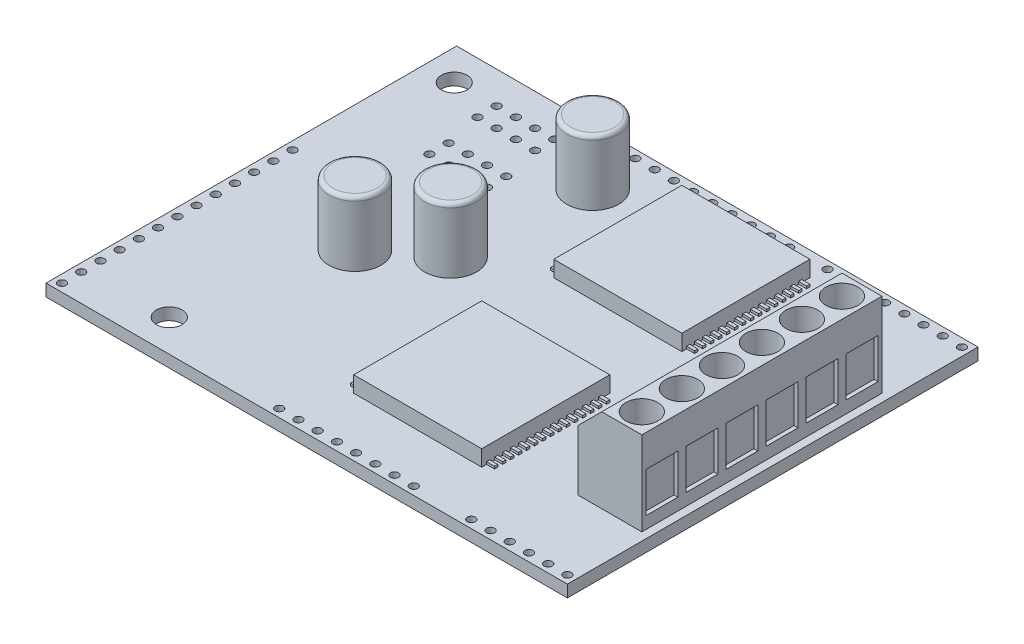
SolidWorks part; units mm, degrees
ref_plane "Спереди" through (0, 0, 0) normal (0, 0, 1) x (1, 0, 0)
ref_plane "Сверху" through (0, 0, 0) normal (0, 1, 0) x (1, 0, 0)
ref_plane "Справа" through (0, 0, 0) normal (1, 0, 0) x (0, 0, -1)
sketch "Эскиз1" plane through (0, 0, 0) normal (0, 1, 0) x (1, 0, 0)
  line L1 (-32.57, 25.65) -> (32.57, 25.65)
  line L2 (-32.57, 25.65) -> (-32.57, -25.65)
  line L3 (-32.57, -25.65) -> (32.57, -25.65)
  line L4 (32.57, 25.65) -> (32.57, -25.65)
  dimension "D1" = 65.14
  dimension "D2" = 51.3
  dimension "D3" = 32.57
  dimension "D4" = 25.65
extrude "Бобышка-Вытянуть1" add sketch "Эскиз1" along normal blind 1.5
sketch "Эскиз2" plane through (0, 1.5, 0) normal (0, 1, 0) x (1, 0, 0)
  line L0 (32.57, -25.65) -> (32.57, 25.65) construction
  line L1 (-1.43, 22.65) -> (14.57, 22.65)
  line L2 (-1.43, 22.65) -> (-1.43, 6.65)
  line L3 (-1.43, 6.65) -> (14.57, 6.65)
  line L4 (14.57, 22.65) -> (14.57, 6.65)
  line L5 (32.57, 25.65) -> (-32.57, 25.65) construction
  line L6 (-1.43, -2.35) -> (14.57, -2.35)
  line L7 (-1.43, -2.35) -> (-1.43, -18.35)
  line L8 (-1.43, -18.35) -> (14.57, -18.35)
  line L9 (14.57, -2.35) -> (14.57, -18.35)
  dimension "D1" = 16
  dimension "D2" = 16
  dimension "D3" = 18
  dimension "D4" = 3
  dimension "D5" = 2
extrude "Бобышка-Вытянуть2" add sketch "Эскиз2" along normal blind 2
sketch "Эскиз3" plane through (0, 1.5, 0) normal (0, 1, 0) x (1, 0, 0)
  line L0 (14.57, 6.65) -> (14.57, 22.65) construction
  line L1 (14.57, 21.65) -> (15.57, 21.65)
  line L2 (14.57, 21.65) -> (14.57, 21.25)
  line L3 (14.57, 21.25) -> (15.57, 21.25)
  line L4 (15.57, 21.65) -> (15.57, 21.25)
  line L5 (14.57, 22.65) -> (-1.43, 22.65) construction
  line L6 (14.57, 20.65) -> (15.57, 20.65)
  line L7 (14.57, 20.65) -> (14.57, 20.25)
  line L8 (14.57, 20.25) -> (15.57, 20.25)
  line L9 (15.57, 20.65) -> (15.57, 20.25)
  line L10 (14.57, 19.65) -> (15.57, 19.65)
  line L11 (14.57, 19.65) -> (14.57, 19.25)
  line L12 (14.57, 19.25) -> (15.57, 19.25)
  line L13 (15.57, 19.65) -> (15.57, 19.25)
  line L14 (14.57, 18.65) -> (15.57, 18.65)
  line L15 (14.57, 18.65) -> (14.57, 18.25)
  line L16 (14.57, 18.25) -> (15.57, 18.25)
  line L17 (15.57, 18.65) -> (15.57, 18.25)
  line L18 (14.57, 17.65) -> (15.57, 17.65)
  line L19 (14.57, 17.65) -> (14.57, 17.25)
  line L20 (14.57, 17.25) -> (15.57, 17.25)
  line L21 (15.57, 17.65) -> (15.57, 17.25)
  line L22 (14.57, 16.65) -> (15.57, 16.65)
  line L23 (14.57, 16.65) -> (14.57, 16.25)
  line L24 (14.57, 16.25) -> (15.57, 16.25)
  line L25 (15.57, 16.65) -> (15.57, 16.25)
  line L26 (14.57, 15.65) -> (15.57, 15.65)
  line L27 (14.57, 15.65) -> (14.57, 15.25)
  line L28 (14.57, 15.25) -> (15.57, 15.25)
  line L29 (15.57, 15.65) -> (15.57, 15.25)
  line L30 (14.57, 14.65) -> (15.57, 14.65)
  line L31 (14.57, 14.65) -> (14.57, 14.25)
  line L32 (14.57, 14.25) -> (15.57, 14.25)
  line L33 (15.57, 14.65) -> (15.57, 14.25)
  line L34 (14.57, 13.65) -> (15.57, 13.65)
  line L35 (14.57, 13.65) -> (14.57, 13.25)
  line L36 (14.57, 13.25) -> (15.57, 13.25)
  line L37 (15.57, 13.65) -> (15.57, 13.25)
  line L38 (14.57, 12.65) -> (15.57, 12.65)
  line L39 (14.57, 12.65) -> (14.57, 12.25)
  line L40 (14.57, 12.25) -> (15.57, 12.25)
  line L41 (15.57, 12.65) -> (15.57, 12.25)
  line L42 (14.57, 11.65) -> (15.57, 11.65)
  line L43 (14.57, 11.65) -> (14.57, 11.25)
  line L44 (14.57, 11.25) -> (15.57, 11.25)
  line L45 (15.57, 11.65) -> (15.57, 11.25)
  line L46 (14.57, 10.65) -> (15.57, 10.65)
  line L47 (14.57, 10.65) -> (14.57, 10.25)
  line L48 (14.57, 10.25) -> (15.57, 10.25)
  line L49 (15.57, 10.65) -> (15.57, 10.25)
  line L50 (14.57, 9.65) -> (15.57, 9.65)
  line L51 (14.57, 9.65) -> (14.57, 9.25)
  line L52 (14.57, 9.25) -> (15.57, 9.25)
  line L53 (15.57, 9.65) -> (15.57, 9.25)
  line L54 (14.57, 8.65) -> (15.57, 8.65)
  line L55 (14.57, 8.65) -> (14.57, 8.25)
  line L56 (14.57, 8.25) -> (15.57, 8.25)
  line L57 (15.57, 8.65) -> (15.57, 8.25)
  line L58 (14.57, 7.65) -> (15.57, 7.65)
  line L59 (14.57, 7.65) -> (14.57, 7.25)
  line L60 (14.57, 7.25) -> (15.57, 7.25)
  line L61 (15.57, 7.65) -> (15.57, 7.25)
  line L62 (6.57, 54.7714) -> (6.57, -83.906) construction
  line L63 (-2.43, 7.65) -> (-2.43, 7.25)
  line L64 (-1.43, 7.25) -> (-2.43, 7.25)
  line L65 (-1.43, 7.65) -> (-1.43, 7.25)
  line L66 (-1.43, 7.65) -> (-2.43, 7.65)
  line L67 (-2.43, 8.65) -> (-2.43, 8.25)
  line L68 (-1.43, 8.25) -> (-2.43, 8.25)
  line L69 (-1.43, 8.65) -> (-1.43, 8.25)
  line L70 (-1.43, 8.65) -> (-2.43, 8.65)
  line L71 (-2.43, 9.65) -> (-2.43, 9.25)
  line L72 (-1.43, 9.25) -> (-2.43, 9.25)
  line L73 (-1.43, 9.65) -> (-1.43, 9.25)
  line L74 (-1.43, 9.65) -> (-2.43, 9.65)
  line L75 (-2.43, 10.65) -> (-2.43, 10.25)
  line L76 (-1.43, 10.25) -> (-2.43, 10.25)
  line L77 (-1.43, 10.65) -> (-1.43, 10.25)
  line L78 (-1.43, 10.65) -> (-2.43, 10.65)
  line L79 (-2.43, 11.65) -> (-2.43, 11.25)
  line L80 (-1.43, 11.25) -> (-2.43, 11.25)
  line L81 (-1.43, 11.65) -> (-1.43, 11.25)
  line L82 (-1.43, 11.65) -> (-2.43, 11.65)
  line L83 (-2.43, 12.65) -> (-2.43, 12.25)
  line L84 (-1.43, 12.25) -> (-2.43, 12.25)
  line L85 (-1.43, 12.65) -> (-1.43, 12.25)
  line L86 (-1.43, 12.65) -> (-2.43, 12.65)
  line L87 (-2.43, 13.65) -> (-2.43, 13.25)
  line L88 (-1.43, 13.25) -> (-2.43, 13.25)
  line L89 (-1.43, 13.65) -> (-1.43, 13.25)
  line L90 (-1.43, 13.65) -> (-2.43, 13.65)
  line L91 (-2.43, 14.65) -> (-2.43, 14.25)
  line L92 (-1.43, 14.25) -> (-2.43, 14.25)
  line L93 (-1.43, 14.65) -> (-1.43, 14.25)
  line L94 (-1.43, 14.65) -> (-2.43, 14.65)
  line L95 (-2.43, 15.65) -> (-2.43, 15.25)
  line L96 (-1.43, 15.25) -> (-2.43, 15.25)
  line L97 (-1.43, 15.65) -> (-1.43, 15.25)
  line L98 (-1.43, 15.65) -> (-2.43, 15.65)
  line L99 (-2.43, 16.65) -> (-2.43, 16.25)
  line L100 (-1.43, 16.25) -> (-2.43, 16.25)
  line L101 (-1.43, 16.65) -> (-1.43, 16.25)
  line L102 (-1.43, 16.65) -> (-2.43, 16.65)
  line L103 (-2.43, 17.65) -> (-2.43, 17.25)
  line L104 (-1.43, 17.25) -> (-2.43, 17.25)
  line L105 (-1.43, 17.65) -> (-1.43, 17.25)
  line L106 (-1.43, 17.65) -> (-2.43, 17.65)
  line L107 (-2.43, 18.65) -> (-2.43, 18.25)
  line L108 (-1.43, 18.25) -> (-2.43, 18.25)
  line L109 (-1.43, 18.65) -> (-1.43, 18.25)
  line L110 (-1.43, 18.65) -> (-2.43, 18.65)
  line L111 (-2.43, 19.65) -> (-2.43, 19.25)
  line L112 (-1.43, 19.25) -> (-2.43, 19.25)
  line L113 (-1.43, 19.65) -> (-1.43, 19.25)
  line L114 (-1.43, 19.65) -> (-2.43, 19.65)
  line L115 (-2.43, 20.65) -> (-2.43, 20.25)
  line L116 (-1.43, 20.25) -> (-2.43, 20.25)
  line L117 (-1.43, 20.65) -> (-1.43, 20.25)
  line L118 (-1.43, 20.65) -> (-2.43, 20.65)
  line L119 (-2.43, 21.65) -> (-2.43, 21.25)
  line L120 (-1.43, 21.25) -> (-2.43, 21.25)
  line L121 (-1.43, 21.65) -> (-1.43, 21.25)
  line L122 (-1.43, 21.65) -> (-2.43, 21.65)
  line L123 (14.57, -3.35) -> (15.57, -3.35)
  line L124 (14.57, -3.35) -> (14.57, -3.75)
  line L125 (14.57, -3.75) -> (15.57, -3.75)
  line L126 (15.57, -3.35) -> (15.57, -3.75)
  line L127 (14.57, -4.35) -> (15.57, -4.35)
  line L128 (14.57, -4.35) -> (14.57, -4.75)
  line L129 (14.57, -4.75) -> (15.57, -4.75)
  line L130 (15.57, -4.35) -> (15.57, -4.75)
  line L131 (14.57, -5.35) -> (15.57, -5.35)
  line L132 (14.57, -5.35) -> (14.57, -5.75)
  line L133 (14.57, -5.75) -> (15.57, -5.75)
  line L134 (15.57, -5.35) -> (15.57, -5.75)
  line L135 (14.57, -6.35) -> (15.57, -6.35)
  line L136 (14.57, -6.35) -> (14.57, -6.75)
  line L137 (14.57, -6.75) -> (15.57, -6.75)
  line L138 (15.57, -6.35) -> (15.57, -6.75)
  line L139 (14.57, -7.35) -> (15.57, -7.35)
  line L140 (14.57, -7.35) -> (14.57, -7.75)
  line L141 (14.57, -7.75) -> (15.57, -7.75)
  line L142 (15.57, -7.35) -> (15.57, -7.75)
  line L143 (14.57, -8.35) -> (15.57, -8.35)
  line L144 (14.57, -8.35) -> (14.57, -8.75)
  line L145 (14.57, -8.75) -> (15.57, -8.75)
  line L146 (15.57, -8.35) -> (15.57, -8.75)
  line L147 (14.57, -9.35) -> (15.57, -9.35)
  line L148 (14.57, -9.35) -> (14.57, -9.75)
  line L149 (14.57, -9.75) -> (15.57, -9.75)
  line L150 (15.57, -9.35) -> (15.57, -9.75)
  line L151 (14.57, -10.35) -> (15.57, -10.35)
  line L152 (14.57, -10.35) -> (14.57, -10.75)
  line L153 (14.57, -10.75) -> (15.57, -10.75)
  line L154 (15.57, -10.35) -> (15.57, -10.75)
  line L155 (14.57, -11.35) -> (15.57, -11.35)
  line L156 (14.57, -11.35) -> (14.57, -11.75)
  line L157 (14.57, -11.75) -> (15.57, -11.75)
  line L158 (15.57, -11.35) -> (15.57, -11.75)
  line L159 (14.57, -12.35) -> (15.57, -12.35)
  line L160 (14.57, -12.35) -> (14.57, -12.75)
  line L161 (14.57, -12.75) -> (15.57, -12.75)
  line L162 (15.57, -12.35) -> (15.57, -12.75)
  line L163 (14.57, -13.35) -> (15.57, -13.35)
  line L164 (14.57, -13.35) -> (14.57, -13.75)
  line L165 (14.57, -13.75) -> (15.57, -13.75)
  line L166 (15.57, -13.35) -> (15.57, -13.75)
  line L167 (14.57, -14.35) -> (15.57, -14.35)
  line L168 (14.57, -14.35) -> (14.57, -14.75)
  line L169 (14.57, -14.75) -> (15.57, -14.75)
  line L170 (15.57, -14.35) -> (15.57, -14.75)
  line L171 (14.57, -15.35) -> (15.57, -15.35)
  line L172 (14.57, -15.35) -> (14.57, -15.75)
  line L173 (14.57, -15.75) -> (15.57, -15.75)
  line L174 (15.57, -15.35) -> (15.57, -15.75)
  line L175 (14.57, -16.35) -> (15.57, -16.35)
  line L176 (14.57, -16.35) -> (14.57, -16.75)
  line L177 (14.57, -16.75) -> (15.57, -16.75)
  line L178 (15.57, -16.35) -> (15.57, -16.75)
  line L179 (14.57, -17.35) -> (15.57, -17.35)
  line L180 (14.57, -17.35) -> (14.57, -17.75)
  line L181 (14.57, -17.75) -> (15.57, -17.75)
  line L182 (15.57, -17.35) -> (15.57, -17.75)
  line L183 (-2.43, -17.35) -> (-2.43, -17.75)
  line L184 (-1.43, -17.75) -> (-2.43, -17.75)
  line L185 (-1.43, -17.35) -> (-1.43, -17.75)
  line L186 (-1.43, -17.35) -> (-2.43, -17.35)
  line L187 (-2.43, -16.35) -> (-2.43, -16.75)
  line L188 (-1.43, -16.75) -> (-2.43, -16.75)
  line L189 (-1.43, -16.35) -> (-1.43, -16.75)
  line L190 (-1.43, -16.35) -> (-2.43, -16.35)
  line L191 (-2.43, -15.35) -> (-2.43, -15.75)
  line L192 (-1.43, -15.75) -> (-2.43, -15.75)
  line L193 (-1.43, -15.35) -> (-1.43, -15.75)
  line L194 (-1.43, -15.35) -> (-2.43, -15.35)
  line L195 (-2.43, -14.35) -> (-2.43, -14.75)
  line L196 (-1.43, -14.75) -> (-2.43, -14.75)
  line L197 (-1.43, -14.35) -> (-1.43, -14.75)
  line L198 (-1.43, -14.35) -> (-2.43, -14.35)
  line L199 (-2.43, -13.35) -> (-2.43, -13.75)
  line L200 (-1.43, -13.75) -> (-2.43, -13.75)
  line L201 (-1.43, -13.35) -> (-1.43, -13.75)
  line L202 (-1.43, -13.35) -> (-2.43, -13.35)
  line L203 (-2.43, -12.35) -> (-2.43, -12.75)
  line L204 (-1.43, -12.75) -> (-2.43, -12.75)
  line L205 (-1.43, -12.35) -> (-1.43, -12.75)
  line L206 (-1.43, -12.35) -> (-2.43, -12.35)
  line L207 (-2.43, -11.35) -> (-2.43, -11.75)
  line L208 (-1.43, -11.75) -> (-2.43, -11.75)
  line L209 (-1.43, -11.35) -> (-1.43, -11.75)
  line L210 (-1.43, -11.35) -> (-2.43, -11.35)
  line L211 (-2.43, -10.35) -> (-2.43, -10.75)
  line L212 (-1.43, -10.75) -> (-2.43, -10.75)
  line L213 (-1.43, -10.35) -> (-1.43, -10.75)
  line L214 (-1.43, -10.35) -> (-2.43, -10.35)
  line L215 (-2.43, -9.35) -> (-2.43, -9.75)
  line L216 (-1.43, -9.75) -> (-2.43, -9.75)
  line L217 (-1.43, -9.35) -> (-1.43, -9.75)
  line L218 (-1.43, -9.35) -> (-2.43, -9.35)
  line L219 (-2.43, -8.35) -> (-2.43, -8.75)
  line L220 (-1.43, -8.75) -> (-2.43, -8.75)
  line L221 (-1.43, -8.35) -> (-1.43, -8.75)
  line L222 (-1.43, -8.35) -> (-2.43, -8.35)
  line L223 (-2.43, -7.35) -> (-2.43, -7.75)
  line L224 (-1.43, -7.75) -> (-2.43, -7.75)
  line L225 (-1.43, -7.35) -> (-1.43, -7.75)
  line L226 (-1.43, -7.35) -> (-2.43, -7.35)
  line L227 (-2.43, -6.35) -> (-2.43, -6.75)
  line L228 (-1.43, -6.75) -> (-2.43, -6.75)
  line L229 (-1.43, -6.35) -> (-1.43, -6.75)
  line L230 (-1.43, -6.35) -> (-2.43, -6.35)
  line L231 (-2.43, -5.35) -> (-2.43, -5.75)
  line L232 (-1.43, -5.75) -> (-2.43, -5.75)
  line L233 (-1.43, -5.35) -> (-1.43, -5.75)
  line L234 (-1.43, -5.35) -> (-2.43, -5.35)
  line L235 (-2.43, -4.35) -> (-2.43, -4.75)
  line L236 (-1.43, -4.75) -> (-2.43, -4.75)
  line L237 (-1.43, -4.35) -> (-1.43, -4.75)
  line L238 (-1.43, -4.35) -> (-2.43, -4.35)
  line L239 (-2.43, -3.35) -> (-2.43, -3.75)
  line L240 (-1.43, -3.75) -> (-2.43, -3.75)
  line L241 (-1.43, -3.35) -> (-1.43, -3.75)
  line L242 (-1.43, -3.35) -> (-2.43, -3.35)
  dimension "D1" = 0.4
  dimension "D2" = 1
  dimension "D3" = 1
  dimension "D5" = 8
  dimension "D6" = 8
  dimension "D4" = 15
  dimension "D7" = 2
extrude "Бобышка-Вытянуть3" add sketch "Эскиз3" along normal blind 0.3
sketch "Эскиз4" plane through (0, 1.5, 0) normal (0, 1, 0) x (1, 0, 0)
  line L0 (32.57, -25.65) -> (32.57, 25.65) construction
  line L1 (-32.57, -25.65) -> (32.57, -25.65) construction
  line L2 (32.57, 25.65) -> (-32.57, 25.65) construction
  line L3 (-32.57, 25.65) -> (-32.57, -25.65) construction
  circle A0 centre (31.57, -24.65) radius 0.5
  circle A1 centre (29.17, -24.65) radius 0.5
  circle A2 centre (26.77, -24.65) radius 0.5
  circle A3 centre (24.37, -24.65) radius 0.5
  circle A4 centre (21.97, -24.65) radius 0.5
  circle A5 centre (19.57, -24.65) radius 0.5
  circle A6 centre (31.57, 24.65) radius 0.5
  circle A7 centre (29.17, 24.65) radius 0.5
  circle A8 centre (12.37, -24.65) radius 0.5
  circle A9 centre (9.97, -24.65) radius 0.5
  circle A10 centre (7.57, -24.65) radius 0.5
  circle A11 centre (5.17, -24.65) radius 0.5
  circle A12 centre (2.77, -24.65) radius 0.5
  circle A13 centre (0.37, -24.65) radius 0.5
  circle A14 centre (-2.03, -24.65) radius 0.5
  circle A15 centre (-4.43, -24.65) radius 0.5
  circle A16 centre (17.17, -24.65) radius 0.5 [skipped]
  circle A17 centre (14.77, -24.65) radius 0.5 [skipped]
  circle A18 centre (26.77, 24.65) radius 0.5
  circle A19 centre (24.37, 24.65) radius 0.5
  circle A20 centre (21.97, 24.65) radius 0.5
  circle A21 centre (19.57, 24.65) radius 0.5
  circle A22 centre (17.17, 24.65) radius 0.5
  circle A23 centre (14.77, 24.65) radius 0.5
  circle A24 centre (-31.57, -24.65) radius 0.5
  circle A25 centre (9.97, 24.65) radius 0.5
  circle A26 centre (7.57, 24.65) radius 0.5
  circle A27 centre (5.17, 24.65) radius 0.5
  circle A28 centre (2.77, 24.65) radius 0.5
  circle A29 centre (0.37, 24.65) radius 0.5
  circle A30 centre (-2.03, 24.65) radius 0.5
  circle A31 centre (-4.43, 24.65) radius 0.5
  circle A32 centre (-6.83, 24.65) radius 0.5
  circle A33 centre (-9.23, 24.65) radius 0.5
  circle A34 centre (-11.63, 24.65) radius 0.5
  circle A35 centre (12.37, 24.65) radius 0.5 [skipped]
  circle A36 centre (-31.57, -22.25) radius 0.5
  circle A37 centre (-31.57, -19.85) radius 0.5
  circle A38 centre (-31.57, -17.45) radius 0.5
  circle A39 centre (-31.57, -15.05) radius 0.5
  circle A40 centre (-31.57, -12.65) radius 0.5
  circle A41 centre (-31.57, -10.25) radius 0.5
  circle A42 centre (-31.57, -7.85) radius 0.5
  circle A43 centre (-31.57, -5.45) radius 0.5
  circle A44 centre (-31.57, -3.05) radius 0.5
  circle A45 centre (-31.57, -0.65) radius 0.5
  circle A46 centre (-31.57, 1.75) radius 0.5
  circle A47 centre (-31.57, 4.15) radius 0.5
  circle A48 centre (-28.77, 21.55) radius 1.6
  circle A49 centre (-21.17, -21.65) radius 1.6
  circle A50 centre (-23.57, 21.65) radius 0.5
  circle A51 centre (-21.17, 21.65) radius 0.5
  circle A52 centre (-18.77, 21.65) radius 0.5
  circle A53 centre (-16.37, 21.65) radius 0.5
  circle A54 centre (-21.17, 19.25) radius 0.5
  circle A55 centre (-18.77, 19.25) radius 0.5
  circle A56 centre (-16.37, 19.25) radius 0.5
  circle A57 centre (-23.57, 19.25) radius 0.5
  circle A58 centre (-22.57, 14.65) radius 0.5
  circle A59 centre (-20.17, 14.65) radius 0.5
  circle A60 centre (-17.77, 14.65) radius 0.5
  circle A61 centre (-15.37, 14.65) radius 0.5
  circle A62 centre (-20.17, 12.25) radius 0.5
  circle A63 centre (-17.77, 12.25) radius 0.5
  circle A64 centre (-15.37, 12.25) radius 0.5
  circle A65 centre (-22.57, 12.25) radius 0.5
  dimension "D1" = 1
  dimension "D5" = 1
  dimension "D9" = 1
  dimension "D12" = 13
  dimension "D13" = 3.2
  dimension "D16" = 3.2
  dimension "D19" = 1
  dimension "D2" = 1
  dimension "D3" = 1
  dimension "D6" = 1
  dimension "D7" = 1
  dimension "D10" = 1
  dimension "D11" = 1
  dimension "D14" = 4.1
  dimension "D15" = 3.8
  dimension "D17" = 4
  dimension "D18" = 11.4
  dimension "D20" = 4
  dimension "D21" = 9
  dimension "D24" = 10
  dimension "D25" = 11
  dimension "D4" = 16
  dimension "D8" = 19
  dimension "D22" = 4
  dimension "D23" = 2
  dimension "D26" = 4
  dimension "D27" = 2
extrude "Вырез-Вытянуть1" cut sketch "Эскиз4" against normal blind 2
sketch "Эскиз5" plane through (0, 1.5, 0) normal (0, 1, 0) x (1, 0, 0)
  line L1 (23.57, 14.65) -> (31.57, 14.65)
  line L2 (23.57, 14.65) -> (23.57, -15.35)
  line L3 (23.57, -15.35) -> (31.57, -15.35)
  line L4 (31.57, 14.65) -> (31.57, -15.35)
  dimension "D1" = 30
  dimension "D2" = 8
  dimension "D3" = 11
  dimension "D4" = 1
extrude "Бобышка-Вытянуть4" add sketch "Эскиз5" along normal blind 10.5
chamfer "Фаска1" distance 3 angle 45 1 edges at (23.57, 12, 0.35)
sketch "Эскиз6" plane through (0, 12, 0) normal (0, 1, 0) x (1, 0, 0)
  line L0 (31.57, 14.65) -> (23.57, 14.65) construction
  line L1 (31.57, -15.35) -> (31.57, 14.65) construction
  circle A0 centre (29.0693, 12.15) radius 2
  circle A1 centre (29.0693, 7.15) radius 2
  circle A2 centre (29.0693, 2.15) radius 2
  circle A3 centre (29.0693, -2.85) radius 2
  circle A4 centre (29.0693, -7.85) radius 2
  circle A5 centre (29.0693, -12.85) radius 2
  dimension "D1" = 4
  dimension "D2" = 2.5
  dimension "D3" = 2.5007
  dimension "D4" = 6
extrude "Вырез-Вытянуть2" cut sketch "Эскиз6" against normal blind 4
sketch "Эскиз7" plane through (31.57, 0, 0) normal (1, 0, 0) x (0, 0, -1)
  line L0 (14.65, 12) -> (14.65, 1.5) construction
  line L1 (14.15, 8) -> (10.15, 8)
  line L2 (14.15, 8) -> (14.15, 3)
  line L3 (14.15, 3) -> (10.15, 3)
  line L4 (10.15, 8) -> (10.15, 3)
  line L5 (-15.35, 1.5) -> (14.65, 1.5) construction
  line L6 (9.15, 8) -> (5.15, 8)
  line L7 (9.15, 8) -> (9.15, 3)
  line L8 (9.15, 3) -> (5.15, 3)
  line L9 (5.15, 8) -> (5.15, 3)
  line L10 (4.15, 8) -> (0.15, 8)
  line L11 (4.15, 8) -> (4.15, 3)
  line L12 (4.15, 3) -> (0.15, 3)
  line L13 (0.15, 8) -> (0.15, 3)
  line L14 (-0.85, 8) -> (-4.85, 8)
  line L15 (-0.85, 8) -> (-0.85, 3)
  line L16 (-0.85, 3) -> (-4.85, 3)
  line L17 (-4.85, 8) -> (-4.85, 3)
  line L18 (-5.85, 8) -> (-9.85, 8)
  line L19 (-5.85, 8) -> (-5.85, 3)
  line L20 (-5.85, 3) -> (-9.85, 3)
  line L21 (-9.85, 8) -> (-9.85, 3)
  line L22 (-10.85, 8) -> (-14.85, 8)
  line L23 (-10.85, 8) -> (-10.85, 3)
  line L24 (-10.85, 3) -> (-14.85, 3)
  line L25 (-14.85, 8) -> (-14.85, 3)
  dimension "D1" = 4
  dimension "D2" = 0.5
  dimension "D3" = 1.5
  dimension "D4" = 5
  dimension "D5" = 6
extrude "Вырез-Вытянуть3" cut sketch "Эскиз7" against normal blind 0.5
sketch "Эскиз8" plane through (7.285, -7.285, 0) normal (-0.7071, 0.7071, 0) x (0, 0, 1)
  line L0 (-14.65, 23.0305) -> (-14.65, 27.2731) construction
  line L1 (15.35, 23.0305) -> (-14.65, 23.0305) construction
  circle A0 centre (-12.15, 25.0305) radius 0.5
  circle A1 centre (-7.15, 25.0305) radius 0.5
  circle A2 centre (-2.15, 25.0305) radius 0.5
  circle A3 centre (2.85, 25.0305) radius 0.5
  circle A4 centre (7.85, 25.0305) radius 0.5
  circle A5 centre (12.85, 25.0305) radius 0.5
  point P2 (-14.65, 25.1518)
  dimension "D1" = 1
  dimension "D2" = 2.5
  dimension "D3" = 2
  dimension "D4" = 6
extrude "Вырез-Вытянуть4" cut sketch "Эскиз8" against normal blind 0.2
sketch "Эскиз9" plane through (0, 1.5, 0) normal (0, 1, 0) x (1, 0, 0)
  line L0 (-32.57, 25.65) -> (-32.57, -25.65) construction
  line L1 (32.57, 25.65) -> (-32.57, 25.65) construction
  circle A0 centre (-8.57, 18.65) radius 3.25
  circle A1 centre (-16.82, -2.8) radius 3.25
  circle A2 centre (-10.12, 2.45) radius 3.25
  dimension "D1" = 6.5
  dimension "D8" = 6.5
  dimension "D9" = 6.5
  dimension "D2" = 24
  dimension "D3" = 7
  dimension "D4" = 22.45
  dimension "D5" = 23.2
  dimension "D6" = 15.75
  dimension "D7" = 28.45
extrude "Бобышка-Вытянуть5" add sketch "Эскиз9" along normal blind 8.1
fillet "Скругление1" radius 0.5 3 edges at (-16.82, 9.6, 6.05) (-10.12, 9.6, 0.8) (-8.57, 9.6, -15.4)
